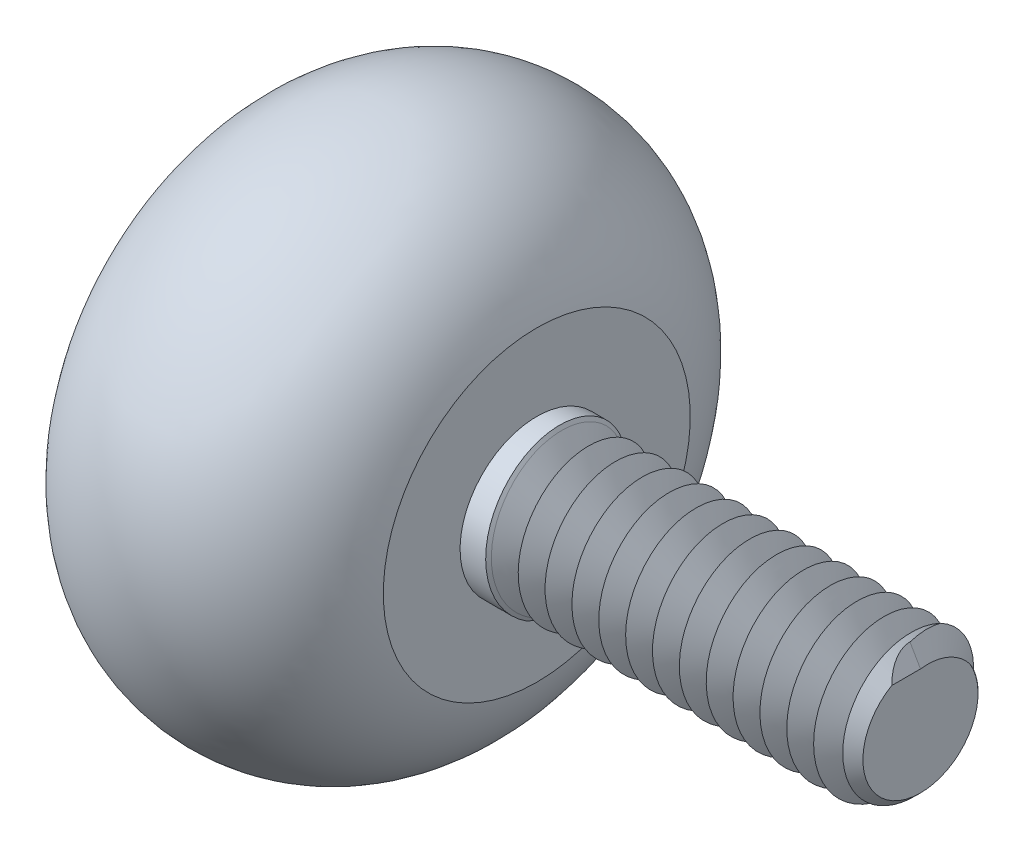
SolidWorks part; units mm, degrees
material "1023 Carbon Steel Sheet (SS)"
ref_plane "Front Plane" through (0, 0, 0) normal (0, 0, 1) x (1, 0, 0)
ref_plane "Top Plane" through (0, 0, 0) normal (0, 1, 0) x (1, 0, 0)
ref_plane "Right Plane" through (0, 0, 0) normal (1, 0, 0) x (0, 0, -1)
sketch "Sketch1" plane through (0, 0, 0) normal (0, 0, 1) x (1, 0, 0)
  line L0 (-9, 0) -> (9, 0) construction
  line L1 (9, 0) -> (9, 2)
  line L2 (9, 2) -> (-1, 2)
  line L3 (-9, 0) -> (-9, 4)
  line L4 (-1, 2) -> (-1, 4)
  line L5 (-9, 0) -> (9, 0)
  arc A0 (-1, 4) -> (-9, 4) centre (-5, 2.9482) ccw
  point P3 (0, 0)
  point P9 (-5, 2)
  point P10 (-5, 2)
  dimension "D1" = 18
  dimension "D2" = 2
  dimension "D3" = 10
  dimension "D4" = 2
  dimension "D5" = 4
revolve "Revolve1" add sketch "Sketch1" angle 360 about L0
chamfer "Chamfer1" distance 0.5 angle 45 1 edges at (9, -2, 0)
sketch "Sketch2" plane through (9, 0, 0) normal (1, 0, 0) x (0, 0, -1)
  circle A4 centre (0, 0) radius 2 construction
  circle A5 centre (0, 0) radius 2
curve "Helix/Spiral1" pitch 0.7 height 9.45 turns 13.5
sketch "Sketch3" plane through (0, 0, 0) normal (0, 0, 1) x (1, 0, 0)
  line L0 (9, 1.3) -> (9, 2) construction
  line L1 (9, 1.3) -> (9.6062, 2.35)
  line L2 (9.6062, 2.35) -> (8.3938, 2.35)
  line L3 (8.3938, 2.35) -> (9, 1.3)
  line L4 (9, -1.5) -> (9, 1.5) construction
  circle A0 centre (9, 2) radius 0.35 construction
  spline S0 degree 3 poles (9, 2) (8.9855, 2) (8.9562, 1.8959) (8.9125, 1.451) (8.8687, 0.7853) (8.825, 0) (8.7812, -0.7853) (8.7375, -1.451) (8.6937, -1.8959) (8.65, -2.0521) (8.6062, -1.8959) (8.5625, -1.451) (8.5187, -0.7853) (8.475, 0) (8.4312, 0.7853) (8.3875, 1.451) (8.3437, 1.8959) (8.3, 2.0521) (8.2562, 1.8959) (8.2125, 1.451) (8.1687, 0.7853) (8.125, 0) (8.0813, -0.7853) (8.0375, -1.451) (7.9937, -1.8959) (7.95, -2.0521) (7.9062, -1.8959) (7.8625, -1.451) (7.8187, -0.7853) (7.775, 0) (7.7313, 0.7853) (7.6875, 1.451) (7.6438, 1.8959) (7.6, 2.0521) (7.5563, 1.8959) (7.5125, 1.451) (7.4688, 0.7853) (7.425, 0) (7.3813, -0.7853) (7.3375, -1.451) (7.2938, -1.8959) (7.25, -2.0521) (7.2063, -1.8959) (7.1625, -1.451) (7.1188, -0.7853) (7.075, 0) (7.0313, 0.7853) (6.9875, 1.451) (6.9438, 1.8959) (6.9, 2.0521) (6.8563, 1.8959) (6.8125, 1.451) (6.7688, 0.7853) (6.725, 0) (6.6813, -0.7853) (6.6375, -1.451) (6.5938, -1.8959) (6.55, -2.0521) (6.5063, -1.8959) (6.4625, -1.451) (6.4188, -0.7853) (6.375, 0) (6.3313, 0.7853) (6.2875, 1.451) (6.2438, 1.8959) (6.2, 2.0521) (6.1563, 1.8959) (6.1125, 1.451) (6.0687, 0.7853) (6.025, 0) (5.9813, -0.7853) (5.9375, -1.451) (5.8937, -1.8959) (5.85, -2.0521) (5.8063, -1.8959) (5.7625, -1.451) (5.7188, -0.7853) (5.675, 0) (5.6313, 0.7853) (5.5875, 1.451) (5.5438, 1.8959) (5.5, 2.0521) (5.4563, 1.8959) (5.4125, 1.451) (5.3688, 0.7853) (5.325, 0) (5.2813, -0.7853) (5.2375, -1.451) (5.1938, -1.8959) (5.15, -2.0521) (5.1063, -1.8959) (5.0625, -1.451) (5.0188, -0.7853) (4.975, 0) (4.9313, 0.7853) (4.8875, 1.451) (4.8438, 1.8959) (4.8, 2.0521) (4.7562, 1.8959) (4.7125, 1.451) (4.6688, 0.7853) (4.625, 0) (4.5812, -0.7853) (4.5375, -1.451) (4.4937, -1.8959) (4.45, -2.0521) (4.4062, -1.8959) (4.3625, -1.451) (4.3187, -0.7853) (4.275, 0) (4.2312, 0.7853) (4.1875, 1.451) (4.1437, 1.8959) (4.1, 2.0521) (4.0562, 1.8959) (4.0125, 1.451) (3.9687, 0.7853) (3.925, 0) (3.8812, -0.7853) (3.8375, -1.451) (3.7937, -1.8959) (3.75, -2.0521) (3.7062, -1.8959) (3.6625, -1.451) (3.6187, -0.7853) (3.575, 0) (3.5312, 0.7853) (3.4875, 1.451) (3.4437, 1.8959) (3.4, 2.0521) (3.3562, 1.8959) (3.3125, 1.451) (3.2687, 0.7853) (3.225, 0) (3.1812, -0.7853) (3.1375, -1.451) (3.0937, -1.8959) (3.05, -2.0521) (3.0062, -1.8959) (2.9625, -1.451) (2.9187, -0.7853) (2.875, 0) (2.8312, 0.7853) (2.7875, 1.451) (2.7437, 1.8959) (2.7, 2.0521) (2.6562, 1.8959) (2.6125, 1.451) (2.5687, 0.7853) (2.525, 0) (2.4812, -0.7853) (2.4375, -1.451) (2.3937, -1.8959) (2.35, -2.0521) (2.3062, -1.8959) (2.2625, -1.451) (2.2187, -0.7853) (2.175, 0) (2.1312, 0.7853) (2.0875, 1.451) (2.0437, 1.8959) (2, 2.0521) (1.9562, 1.8959) (1.9125, 1.451) (1.8687, 0.7853) (1.825, 0) (1.7812, -0.7853) (1.7375, -1.451) (1.6937, -1.8959) (1.65, -2.0521) (1.6062, -1.8959) (1.5625, -1.451) (1.5187, -0.7853) (1.475, 0) (1.4312, 0.7853) (1.3875, 1.451) (1.3437, 1.8959) (1.3, 2.0521) (1.2562, 1.8959) (1.2125, 1.451) (1.1687, 0.7853) (1.125, 0) (1.0812, -0.7853) (1.0375, -1.451) (0.9937, -1.8959) (0.95, -2.0521) (0.9062, -1.8959) (0.8625, -1.451) (0.8187, -0.7853) (0.775, 0) (0.7312, 0.7853) (0.6875, 1.451) (0.6437, 1.8959) (0.6, 2.0521) (0.5562, 1.8959) (0.5125, 1.451) (0.4687, 0.7853) (0.425, 0) (0.3812, -0.7853) (0.3375, -1.451) (0.2937, -1.8959) (0.25, -2.0521) (0.2063, -1.8959) (0.1625, -1.451) (0.1188, -0.7853) (0.075, 0) (0.0313, 0.7853) (-0.0125, 1.451) (-0.0562, 1.8959) (-0.1, 2.0521) (-0.1437, 1.8959) (-0.1875, 1.451) (-0.2312, 0.7853) (-0.275, 0) (-0.3187, -0.7853) (-0.3625, -1.451) (-0.4062, -1.8959) (-0.4355, -2) (-0.45, -2) knots 0 0 0 0 0.00463 0.009259 0.013889 0.018519 0.023148 0.027778 0.032407 0.037037 0.041667 0.046296 0.050926 0.055556 0.060185 0.064815 0.069444 0.074074 0.078704 0.083333 0.087963 0.092593 0.097222 0.101852 0.106481 0.111111 0.115741 0.12037 0.125 0.12963 0.134259 0.138889 0.143519 0.148148 0.152778 0.157407 0.162037 0.166667 0.171296 0.175926 0.180556 0.185185 0.189815 0.194444 0.199074 0.203704 0.208333 0.212963 0.217593 0.222222 0.226852 0.231481 0.236111 0.240741 0.24537 0.25 0.25463 0.259259 0.263889 0.268519 0.273148 0.277778 0.282407 0.287037 0.291667 0.296296 0.300926 0.305556 0.310185 0.314815 0.319444 0.324074 0.328704 0.333333 0.337963 0.342593 0.347222 0.351852 0.356481 0.361111 0.365741 0.37037 0.375 0.37963 0.384259 0.388889 0.393519 0.398148 0.402778 0.407407 0.412037 0.416667 0.421296 0.425926 0.430556 0.435185 0.439815 0.444444 0.449074 0.453704 0.458333 0.462963 0.467593 0.472222 0.476852 0.481481 0.486111 0.490741 0.49537 0.5 0.50463 0.509259 0.513889 0.518519 0.523148 0.527778 0.532407 0.537037 0.541667 0.546296 0.550926 0.555556 0.560185 0.564815 0.569444 0.574074 0.578704 0.583333 0.587963 0.592593 0.597222 0.601852 0.606481 0.611111 0.615741 0.62037 0.625 0.62963 0.634259 0.638889 0.643519 0.648148 0.652778 0.657407 0.662037 0.666667 0.671296 0.675926 0.680556 0.685185 0.689815 0.694444 0.699074 0.703704 0.708333 0.712963 0.717593 0.722222 0.726852 0.731481 0.736111 0.740741 0.74537 0.75 0.75463 0.759259 0.763889 0.768519 0.773148 0.777778 0.782407 0.787037 0.791667 0.796296 0.800926 0.805556 0.810185 0.814815 0.819444 0.824074 0.828704 0.833333 0.837963 0.842593 0.847222 0.851852 0.856481 0.861111 0.865741 0.87037 0.875 0.87963 0.884259 0.888889 0.893519 0.898148 0.902778 0.907407 0.912037 0.916667 0.921296 0.925926 0.930556 0.935185 0.939815 0.944444 0.949074 0.953704 0.958333 0.962963 0.967593 0.972222 0.976852 0.981481 0.986111 0.990741 0.99537 1 1 1 1 construction
  point P1 (0, 0)
  point P6 (0, 0)
  dimension "D1" = 0.7
sweep "Cut-Sweep1" cut profiles "Sketch3" path "Helix/Spiral1"
sketch "Sketch4" plane through (0, 0, 0) normal (0, 0, -1) x (-1, 0, 0)
  line L5 (0.1541, -2) -> (0.8541, -2)
  line L6 (0.8541, -2) -> (0.8, -1.9062)
  line L7 (0.8, -1.9062) -> (0.45, -1.3)
  line L8 (0.45, -1.3) -> (0.1, -1.9062)
  line L9 (0.1, -1.9062) -> (0.1541, -2)
  line L10 (0.1541, -2) -> (0.8541, -2)
  line L11 (0.8541, -2) -> (0.8, -1.9062)
  line L12 (0.8, -1.9062) -> (0.45, -1.3)
  line L13 (0.45, -1.3) -> (0.1, -1.9062)
  line L14 (0.1, -1.9062) -> (0.1541, -2)
  dimension "D1" = 0
extrude "Cut-Extrude1" cut sketch "Sketch4" against normal blind 10
sketch "Sketch5" plane through (0, 0, 0) normal (0, 0, -1) x (-1, 0, 0)
  line L3 (-9, 1.3) -> (-8.7268, 1.7732)
  line L4 (-8.7268, 1.7732) -> (-9, 1.5)
  line L5 (-9, 1.5) -> (-9, 1.3)
  line L6 (-9, 1.3) -> (-8.7268, 1.7732)
  line L7 (-8.7268, 1.7732) -> (-9, 1.5)
  line L8 (-9, 1.5) -> (-9, 1.3)
  dimension "D1" = 0
extrude "Cut-Extrude2" cut sketch "Sketch5" against normal blind 10
